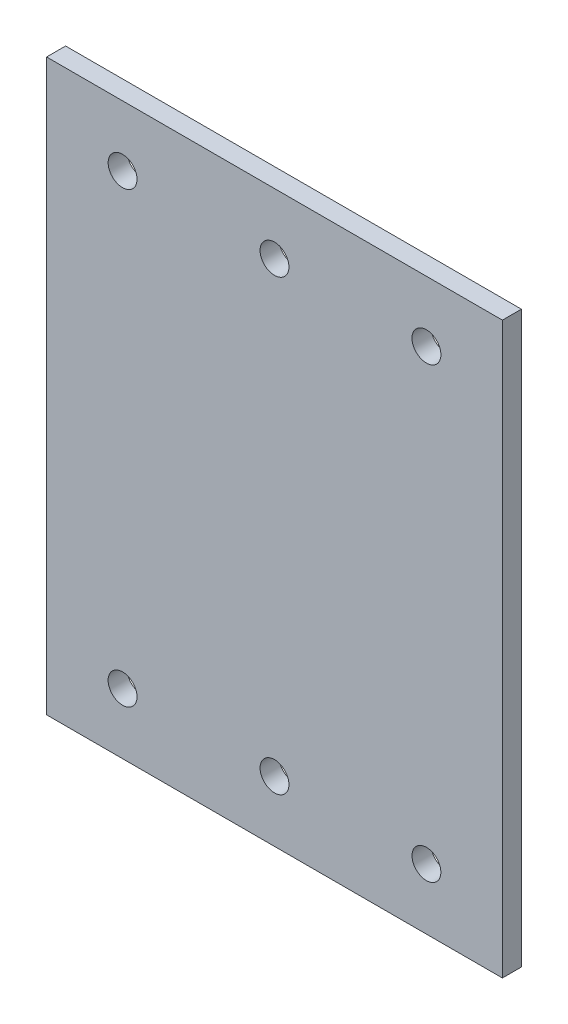
SolidWorks part; units mm, degrees
material "6061 Alloy"
ref_plane "Front Plane" through (0, 0, 0) normal (0, 0, 1) x (1, 0, 0)
ref_plane "Top Plane" through (0, 0, 0) normal (0, 1, 0) x (1, 0, 0)
ref_plane "Right Plane" through (0, 0, 0) normal (1, 0, 0) x (0, 0, -1)
sketch "Sketch1" plane through (0, 0, 0) normal (0, 0, 1) x (1, 0, 0)
  line L0 (38.1, 95.25) -> (38.1, 0) construction
  line L1 (0, 0) -> (76.2, 0)
  line L2 (0, 0) -> (0, 95.25)
  line L3 (0, 95.25) -> (76.2, 95.25)
  line L4 (76.2, 0) -> (76.2, 95.25)
  line L5 (0, 47.625) -> (76.2, 47.625) construction
  line L6 (12.7, 10.16) -> (12.7, 0) construction
  circle A0 centre (12.7, 85.09) radius 2.413
  circle A1 centre (38.1, 85.09) radius 2.413
  circle A2 centre (63.5, 85.09) radius 2.413
  circle A3 centre (63.5, 10.16) radius 2.413
  circle A4 centre (38.1, 10.16) radius 2.413
  circle A5 centre (12.7, 10.16) radius 2.413
  dimension "D3" = 4.826
  dimension "D1" = 95.25
  dimension "D2" = 76.2
  dimension "D4" = 12.7
  dimension "D6" = 10.16
  dimension "D5" = 3
extrude "Boss-Extrude1" add sketch "Sketch1" along normal blind 3.175
